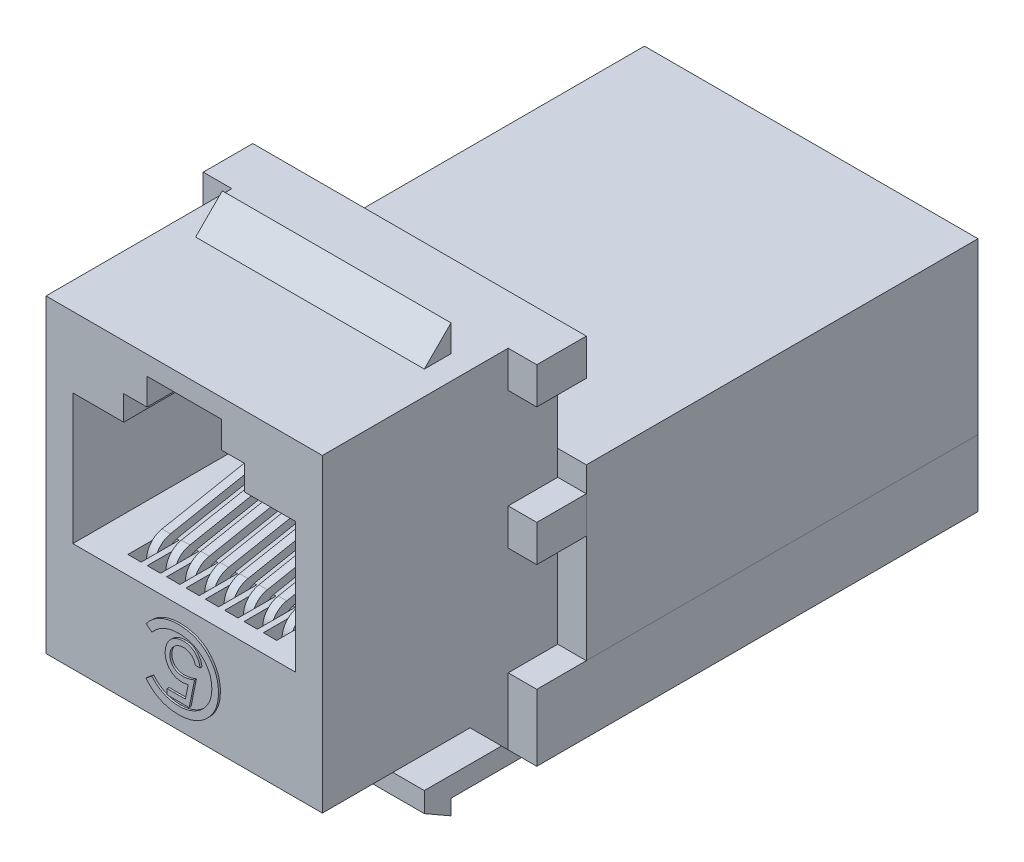
SolidWorks part; units mm, degrees
ref_plane "Front Plane" through (0, 0, 0) normal (0, 0, 1) x (1, 0, 0)
ref_plane "Top Plane" through (0, 0, 0) normal (0, 1, 0) x (1, 0, 0)
ref_plane "Right Plane" through (0, 0, 0) normal (1, 0, 0) x (0, 0, -1)
sketch "Sketch1" plane through (0, 0, 0) normal (0, 0, 1) x (1, 0, 0)
  line L1 (-7.25, 8.125) -> (7.25, 8.125)
  line L2 (-7.25, 8.125) -> (-7.25, -8.125)
  line L3 (-7.25, -8.125) -> (7.25, -8.125)
  line L4 (7.25, 8.125) -> (7.25, -8.125)
  line L5 (-7.25, 8.125) -> (7.25, -8.125) construction
  line L6 (-7.25, -8.125) -> (7.25, 8.125) construction
  point P0 (0, 0)
  dimension "D1" = 14.5
  dimension "D2" = 16.25
extrude "Boss-Extrude1" add sketch "Sketch1" against normal blind 12.35
sketch "Sketch2" plane through (0, 0, 0) normal (0, 0, 1) x (1, 0, 0)
  line L0 (-5.842, -2.425) -> (5.842, -2.425)
  line L1 (5.842, -2.425) -> (5.842, 4.425)
  line L2 (7.25, 8.125) -> (-7.25, 8.125) construction
  line L6 (5.842, 4.425) -> (3.175, 4.425)
  line L7 (3.175, 4.425) -> (3.175, 5.725)
  line L8 (3.175, 5.725) -> (1.95, 5.725)
  line L9 (1.95, 5.725) -> (1.95, 7.125)
  line L10 (1.95, 7.125) -> (-1.95, 7.125)
  line L11 (-1.95, 7.125) -> (-1.95, 5.725)
  line L12 (-1.95, 5.725) -> (-3.175, 5.725)
  line L13 (-3.175, 5.725) -> (-3.175, 4.425)
  line L14 (-3.175, 4.425) -> (-5.842, 4.425)
  line L19 (-5.842, 4.425) -> (-5.842, -2.425)
  line L20 (0, -1000) -> (0, 1000) construction
  line L22 (-3.175, 4.425) -> (-3.175, -2.425) construction
  dimension "D1" = 3.9
  dimension "D2" = 6.35
  dimension "D3" = 11.684
  dimension "D4" = 1
  dimension "D6" = 6.85
  dimension "D8" = 9.55
  dimension "D9" = 1.4
extrude "Cut-Extrude1" cut sketch "Sketch2" against normal blind 10
sketch "Sketch3" plane through (0, 0, -12.35) normal (0, 0, -1) x (-1, 0, 0)
  line L0 (-6.2, 7.125) -> (-6.2, 4.95)
  line L1 (-6.2, 4.95) -> (-3.175, 4.95)
  line L2 (-3.175, 4.95) -> (-3.175, 2.125)
  line L3 (-3.175, 2.125) -> (3.175, 2.125)
  line L4 (3.175, 2.125) -> (3.175, 4.95)
  line L5 (3.175, 4.95) -> (6.2, 4.95)
  line L6 (6.2, 4.95) -> (6.2, 7.125)
  line L7 (6.2, 7.125) -> (-6.2, 7.125)
  line L8 (-1.95, 7.125) -> (1.95, 7.125) construction
  line L9 (7.25, 8.125) -> (7.25, -8.125) construction
  line L10 (-7.25, -8.125) -> (-7.25, 8.125) construction
  line L12 (-3.175, 4.425) -> (-3.175, 5.725) construction
  line L13 (3.175, 5.725) -> (3.175, 4.425) construction
  dimension "D1" = 1.05
  dimension "D2" = 1.05
  dimension "D3" = 2.175
  dimension "D4" = 5
extrude "Cut-Extrude2" cut sketch "Sketch3" against normal blind 10.35
sketch "Sketch4" plane through (0, 0, -12.35) normal (0, 0, -1) x (-1, 0, 0)
  line L0 (7.25, -8.125) -> (-7.25, -8.125) construction
  line L1 (-8.75, -6.625) -> (8.75, -6.625)
  line L2 (-8.75, -6.625) -> (-8.75, -10.125)
  line L3 (-8.75, -10.125) -> (8.75, -10.125)
  line L4 (8.75, -6.625) -> (8.75, -10.125)
  line L5 (-8.75, -6.625) -> (8.75, -10.125) construction
  line L6 (-8.75, -10.125) -> (8.75, -6.625) construction
  point P0 (0, -8.375)
  dimension "D1" = 17.5
  dimension "D2" = 2
  dimension "D3" = 3.5
extrude "Boss-Extrude2" add sketch "Sketch4" along normal blind 20.55 and the other way blind 2.6
chamfer "Chamfer1" distance 2 angle 45 1 edges at (0, -8.125, -9.75)
sketch "Sketch5" plane through (0, 0, -12.35) normal (0, 0, -1) x (-1, 0, 0)
  line L0 (-7.25, -6.625) -> (-7.25, 8.125) construction
  line L1 (-8.75, 0.96) -> (-7.25, 0.96)
  line L2 (-8.75, 0.96) -> (-8.75, -0.96)
  line L3 (-8.75, -0.96) -> (-7.25, -0.96)
  line L4 (-7.25, 0.96) -> (-7.25, -0.96)
  line L5 (7.25, 8.125) -> (7.25, -6.625) construction
  line L6 (7.25, 0.96) -> (8.75, 0.96)
  line L7 (7.25, 0.96) -> (7.25, -0.96)
  line L8 (7.25, -0.96) -> (8.75, -0.96)
  line L9 (8.75, 0.96) -> (8.75, -0.96)
  line L10 (8.75, -10.125) -> (8.75, -6.625) construction
  line L11 (-7.25, 8.125) -> (-8.75, 8.125)
  line L12 (-7.25, 8.125) -> (-7.25, 6.205)
  line L13 (-7.25, 6.205) -> (-8.75, 6.205)
  line L14 (-8.75, 8.125) -> (-8.75, 6.205)
  line L15 (7.25, 8.125) -> (8.75, 8.125)
  line L16 (7.25, 8.125) -> (7.25, 6.205)
  line L17 (7.25, 6.205) -> (8.75, 6.205)
  line L18 (8.75, 8.125) -> (8.75, 6.205)
  point P24 (8.75, 0)
  dimension "D1" = 1.92
extrude "Boss-Extrude3" add sketch "Sketch5" against normal up to surface (2.6 mm away) up to face at (-8, -8.375, -9.75)
sketch "Sketch6" plane through (0, 0, 0) normal (1, 0, 0) x (0, 0, -1)
  line L0 (8, 9.525) -> (8, 8.125)
  line L1 (8, 8.125) -> (6.6, 8.125)
  line L2 (6.6, 8.125) -> (8, 9.525)
  line L3 (9.75, 8.125) -> (0, 8.125) construction
  line L4 (12.35, 6.205) -> (12.35, 8.125) construction
  line L5 (7.75, -8.125) -> (0, -8.125) construction
  dimension "D1" = 4.35
  dimension "D2" = 17.65
extrude "Boss-Extrude4" add sketch "Sketch6" along normal mid plane 12
sketch "Sketch7" plane through (0, 0, -12.35) normal (0, 0, -1) x (-1, 0, 0)
  line L0 (-7.25, -6.625) -> (7.25, -6.625) construction
  line L1 (-8.75, 2.275) -> (8.75, 2.275)
  line L2 (-8.75, 2.275) -> (-8.75, -6.625)
  line L3 (-8.75, -6.625) -> (8.75, -6.625)
  line L4 (8.75, 2.275) -> (8.75, -6.625)
  line L5 (-8.75, 2.275) -> (8.75, -6.625) construction
  line L6 (-8.75, -6.625) -> (8.75, 2.275) construction
  line L7 (-8.75, -10.125) -> (8.75, -10.125) construction
  line L9 (-8.75, 0.96) -> (-8.75, -0.96) construction
  line L11 (7.25, -5.8621) -> (-7.25, -5.8621)
  line L12 (7.25, -5.8621) -> (7.25, 1.5121)
  line L13 (7.25, 1.5121) -> (-7.25, 1.5121)
  line L14 (-7.25, -5.8621) -> (-7.25, 1.5121)
  line L15 (7.25, -5.8621) -> (-7.25, 1.5121) construction
  line L16 (7.25, 1.5121) -> (-7.25, -5.8621) construction
  point P0 (0, -2.175)
  point P10 (0, -2.175)
  dimension "D1" = 12.4
  dimension "D2" = 1.5
extrude "Boss-Extrude5" add sketch "Sketch7" along normal blind 20.55 separate body
sketch "Sketch8" plane through (0, 0, -32.9) normal (0, 0, -1) x (-1, 0, 0)
  line L1 (-7.25, 1.5121) -> (7.25, 1.5121)
  line L2 (-7.25, 1.5121) -> (-7.25, -5.8621)
  line L3 (-7.25, -5.8621) -> (7.25, -5.8621)
  line L4 (7.25, 1.5121) -> (7.25, -5.8621)
extrude "Boss-Extrude6" add sketch "Sketch8" against normal blind 1.5
sketch "Sketch9" plane through (0, 0, 0) normal (1, 0, 0) x (0, 0, -1)
  line L0 (17.9, -10.125) -> (17.9, -12.075)
  line L1 (17.9, -12.075) -> (8, -12.075)
  line L2 (8, -12.075) -> (8, -12.875)
  line L3 (8, -12.875) -> (6.6, -12.075)
  line L4 (6.6, -12.075) -> (6.6, -11.025)
  line L5 (6.6, -11.025) -> (14, -11.025)
  line L6 (14, -11.025) -> (14, -10.125)
  line L7 (14, -10.125) -> (17.9, -10.125)
  line L8 (9.75, -10.125) -> (32.9, -10.125) construction
  line L9 (8, 8.125) -> (8, 9.525) construction
  line L10 (9.75, 8.125) -> (0, 8.125) construction
  line L11 (32.9, -10.125) -> (32.9, -6.625) construction
  dimension "D1" = 20.2
  dimension "D2" = 1.05
  dimension "D3" = 22.4
  dimension "D4" = 3.9
  dimension "D5" = 15
extrude "Boss-Extrude7" add sketch "Sketch9" along normal mid plane 12
sketch "Sketch11" plane through (0, 0, 0) normal (0, 0, 1) x (1, 0, 0)
  line L0 (5.842, -3.325) -> (-5.842, -3.325) construction
  line L1 (-5.842, -2.425) -> (5.842, -2.425) construction
  line L2 (5.842, -3.925) -> (-5.842, -3.925) construction
  text T0 "C" font "Century Gothic" height 3.9
  text T1 "5" font "Century Gothic" height 2.8
  dimension "D1" = 0.9
  dimension "D2" = 0.6
extrude "Boss-Extrude8" add sketch "Sketch11" along normal blind 0.1
sketch "Sketch12" plane through (0, 0, -32.9) normal (0, 0, -1) x (-1, 0, 0)
  line L0 (0, -6.625) -> (0, 2.275) construction
  line L1 (8.75, -6.625) -> (-8.75, -6.625) construction
  line L2 (8.75, 2.275) -> (-8.75, 2.275) construction
  circle A0 centre (0, -2.175) radius 2
  point P9 (0, -2.175)
  dimension "D1" = 4
extrude "Cut-Extrude3" cut sketch "Sketch12" against normal up to next (1.5 mm away)
sketch "Sketch13" plane through (0, -2.425, 0) normal (0, 1, 0) x (1, 0, 0)
  line L0 (-5.842, 0) -> (5.842, 0) construction
  line L1 (-3.9052, 2.95) -> (-3.2067, 2.95)
  line L2 (-3.9052, 2.95) -> (-3.9052, 0.95)
  line L3 (-3.9052, 0.95) -> (-3.2067, 0.95)
  line L4 (-3.2067, 2.95) -> (-3.2067, 0.95)
  line L5 (-3.9052, 2.95) -> (-3.2067, 0.95) construction
  line L6 (-3.9052, 0.95) -> (-3.2067, 2.95) construction
  line L7 (-2.8892, 2.95) -> (-2.1907, 2.95)
  line L8 (-2.8892, 2.95) -> (-2.8892, 0.95)
  line L9 (-2.8892, 0.95) -> (-2.1907, 0.95)
  line L10 (-2.1907, 2.95) -> (-2.1907, 0.95)
  line L11 (-2.8892, 2.95) -> (-2.1907, 0.95) construction
  line L12 (-2.8892, 0.95) -> (-2.1907, 2.95) construction
  line L13 (-1.8732, 2.95) -> (-1.1747, 2.95)
  line L14 (-1.8732, 2.95) -> (-1.8732, 0.95)
  line L15 (-1.8732, 0.95) -> (-1.1747, 0.95)
  line L16 (-1.1747, 2.95) -> (-1.1747, 0.95)
  line L17 (-1.8732, 2.95) -> (-1.1747, 0.95) construction
  line L18 (-1.8732, 0.95) -> (-1.1747, 2.95) construction
  line L19 (-0.8572, 2.95) -> (-0.1587, 2.95)
  line L20 (-0.8572, 2.95) -> (-0.8572, 0.95)
  line L21 (-0.8572, 0.95) -> (-0.1587, 0.95)
  line L22 (-0.1587, 2.95) -> (-0.1587, 0.95)
  line L23 (-0.8572, 2.95) -> (-0.1587, 0.95) construction
  line L24 (-0.8572, 0.95) -> (-0.1587, 2.95) construction
  line L25 (0.1588, 2.95) -> (0.8573, 2.95)
  line L26 (0.1588, 2.95) -> (0.1588, 0.95)
  line L27 (0.1588, 0.95) -> (0.8573, 0.95)
  line L28 (0.8573, 2.95) -> (0.8573, 0.95)
  line L29 (0.1588, 2.95) -> (0.8573, 0.95) construction
  line L30 (0.1588, 0.95) -> (0.8573, 2.95) construction
  line L31 (1.1747, 2.95) -> (1.8733, 2.95)
  line L32 (1.1747, 2.95) -> (1.1748, 0.95)
  line L33 (1.1748, 0.95) -> (1.8733, 0.95)
  line L34 (1.8733, 2.95) -> (1.8733, 0.95)
  line L35 (1.1747, 2.95) -> (1.8733, 0.95) construction
  line L36 (1.1748, 0.95) -> (1.8733, 2.95) construction
  line L37 (2.1908, 2.95) -> (2.8893, 2.95)
  line L38 (2.1908, 2.95) -> (2.1908, 0.95)
  line L39 (2.1908, 0.95) -> (2.8893, 0.95)
  line L40 (2.8893, 2.95) -> (2.8893, 0.95)
  line L41 (2.1908, 2.95) -> (2.8893, 0.95) construction
  line L42 (2.1908, 0.95) -> (2.8893, 2.95) construction
  line L43 (3.2068, 2.95) -> (3.9053, 2.95)
  line L44 (3.2068, 2.95) -> (3.2068, 0.95)
  line L45 (3.2068, 0.95) -> (3.9053, 0.95)
  line L46 (3.9053, 2.95) -> (3.9053, 0.95)
  line L47 (3.2068, 2.95) -> (3.9053, 0.95) construction
  line L48 (3.2068, 0.95) -> (3.9053, 2.95) construction
  line L49 (0, -1000) -> (0, 49000) construction
  point P0 (-3.556, 1.95)
  point P7 (-2.54, 1.95)
  point P12 (-1.524, 1.95)
  point P17 (-0.508, 1.95)
  point P22 (0.508, 1.95)
  point P27 (1.524, 1.95)
  point P32 (2.54, 1.95)
  point P37 (3.556, 1.95)
  point P45 (0, 0)
  dimension "D1" = 0.95
  dimension "D2" = 0.6985
  dimension "D3" = 2.95
  dimension "D4" = 0.6985
  dimension "D5" = 1.016
  dimension "D6" = 0.6985
  dimension "D7" = 0.6985
  dimension "D8" = 1.016
  dimension "D9" = 1.016
  dimension "D10" = 0.6985
  dimension "D11" = 0.6985
  dimension "D12" = 1.016
  dimension "D13" = 0.6985
  dimension "D14" = 0.6985
  dimension "D15" = 1.016
  dimension "D16" = 1.016
  dimension "D17" = 1.016
extrude "Cut-Extrude4" cut sketch "Sketch13" against normal blind 1
sketch "Sketch14" plane through (0, 0, -10) normal (0, 0, 1) x (1, 0, 0)
  line L0 (-3.9052, -0.425) -> (-3.2067, -0.425)
  line L1 (-3.9052, -0.425) -> (-3.9052, -2.425)
  line L2 (-3.9052, -2.425) -> (-3.2067, -2.425)
  line L3 (-3.2067, -0.425) -> (-3.2067, -2.425)
  line L4 (-3.9052, -0.425) -> (-3.2067, -2.425) construction
  line L5 (-3.9052, -2.425) -> (-3.2067, -0.425) construction
  line L6 (-2.8893, -0.425) -> (-2.1907, -0.425)
  line L7 (-2.8893, -0.425) -> (-2.8892, -2.425)
  line L8 (-2.8892, -2.425) -> (-2.1907, -2.425)
  line L9 (-2.1907, -0.425) -> (-2.1907, -2.425)
  line L10 (-2.8893, -0.425) -> (-2.1907, -2.425) construction
  line L11 (-2.8892, -2.425) -> (-2.1907, -0.425) construction
  line L12 (-1.8733, -0.425) -> (-1.1747, -0.425)
  line L13 (-1.8733, -0.425) -> (-1.8732, -2.425)
  line L14 (-1.8732, -2.425) -> (-1.1747, -2.425)
  line L15 (-1.1747, -0.425) -> (-1.1747, -2.425)
  line L16 (-1.8733, -0.425) -> (-1.1747, -2.425) construction
  line L17 (-1.8732, -2.425) -> (-1.1747, -0.425) construction
  line L18 (-0.8573, -0.425) -> (-0.1588, -0.425)
  line L19 (-0.8573, -0.425) -> (-0.8572, -2.425)
  line L20 (-0.8572, -2.425) -> (-0.1587, -2.425)
  line L21 (-0.1588, -0.425) -> (-0.1587, -2.425)
  line L22 (-0.8573, -0.425) -> (-0.1587, -2.425) construction
  line L23 (-0.8572, -2.425) -> (-0.1588, -0.425) construction
  line L24 (0.1587, -0.425) -> (0.8572, -0.425)
  line L25 (0.1587, -0.425) -> (0.1588, -2.425)
  line L26 (0.1588, -2.425) -> (0.8573, -2.425)
  line L27 (0.8572, -0.425) -> (0.8573, -2.425)
  line L28 (0.1587, -0.425) -> (0.8573, -2.425) construction
  line L29 (0.1588, -2.425) -> (0.8572, -0.425) construction
  line L30 (1.1747, -0.425) -> (1.8732, -0.425)
  line L31 (1.1747, -0.425) -> (1.1747, -2.425)
  line L32 (1.1747, -2.425) -> (1.8733, -2.425)
  line L33 (1.8732, -0.425) -> (1.8733, -2.425)
  line L34 (1.1747, -0.425) -> (1.8733, -2.425) construction
  line L35 (1.1747, -2.425) -> (1.8732, -0.425) construction
  line L36 (2.1907, -0.425) -> (2.8893, -0.425)
  line L37 (2.1907, -0.425) -> (2.1908, -2.425)
  line L38 (2.1908, -2.425) -> (2.8893, -2.425)
  line L39 (2.8893, -0.425) -> (2.8893, -2.425)
  line L40 (2.1907, -0.425) -> (2.8893, -2.425) construction
  line L41 (2.1908, -2.425) -> (2.8893, -0.425) construction
  line L42 (3.2067, -0.425) -> (3.9052, -0.425)
  line L43 (3.2067, -0.425) -> (3.2067, -2.425)
  line L44 (3.2067, -2.425) -> (3.9052, -2.425)
  line L45 (3.9052, -0.425) -> (3.9052, -2.425)
  line L46 (3.2067, -0.425) -> (3.9052, -2.425) construction
  line L47 (3.2067, -2.425) -> (3.9052, -0.425) construction
  line L48 (0, -1003.6041) -> (0, 48996.3959) construction
  line L49 (-5.842, -2.425) -> (5.842, -2.425) construction
  line L50 (-4.9213, -0.425) -> (-4.2227, -0.425)
  line L51 (-4.9213, -0.425) -> (-4.9213, -2.425)
  line L52 (-4.9213, -2.425) -> (-4.2227, -2.425)
  line L53 (-4.2227, -0.425) -> (-4.2227, -2.425)
  line L54 (-4.9213, -0.425) -> (-4.2227, -2.425) construction
  line L55 (-4.9213, -2.425) -> (-4.2227, -0.425) construction
  line L56 (4.2227, -0.425) -> (4.9212, -0.425)
  line L57 (4.2227, -0.425) -> (4.2227, -2.425)
  line L58 (4.2227, -2.425) -> (4.9212, -2.425)
  line L59 (4.9212, -0.425) -> (4.9212, -2.425)
  line L60 (4.2227, -0.425) -> (4.9212, -2.425) construction
  line L61 (4.2227, -2.425) -> (4.9212, -0.425) construction
  point P0 (-3.556, -1.425)
  point P5 (-2.54, -1.425)
  point P10 (-1.524, -1.425)
  point P15 (-0.508, -1.425)
  point P20 (0.508, -1.425)
  point P25 (1.524, -1.425)
  point P30 (2.54, -1.425)
  point P35 (3.556, -1.425)
  point P45 (-4.572, -1.425)
  point P50 (4.572, -1.425)
  dimension "D1" = 0.6985
  dimension "D2" = 0.6985
  dimension "D3" = 1.016
  dimension "D4" = 0.6985
  dimension "D5" = 0.6985
  dimension "D6" = 1.016
  dimension "D7" = 1.016
  dimension "D8" = 0.6985
  dimension "D9" = 0.6985
  dimension "D10" = 1.016
  dimension "D11" = 0.6985
  dimension "D12" = 0.6985
  dimension "D13" = 1.016
  dimension "D14" = 1.016
  dimension "D15" = 1.016
  dimension "D16" = 2
  dimension "D17" = 0.6985
  dimension "D18" = 2
  dimension "D19" = 1.016
  dimension "D20" = 0.6985
  dimension "D21" = 2
  dimension "D22" = 1.016
extrude "Cut-Extrude5" cut sketch "Sketch14" against normal blind 1
ref_plane "Plane2" through (-3.7782, 0, 0) normal (1, 0, 0) x (0, 0, -1)
sketch "Sketch15" plane through (-3.7782, 0, 0) normal (1, 0, 0) x (0, 0, -1)
  line L0 (11, -0.425) -> (2.617, -2.0337)
  line L1 (1.8055, -3.0158) -> (1.8055, -3.425)
  line L2 (1.8055, -3.425) -> (2.25, -3.425)
  line L3 (2.25, -3.425) -> (2.25, -3.375)
  line L4 (3.0615, -2.3929) -> (11, -0.8695)
  line L5 (11, -0.8695) -> (11, -0.425)
  line L6 (11, -0.425) -> (11, -2.425) construction
  line L9 (2.95, -3.425) -> (0.95, -3.425) construction
  arc A0 (2.25, -3.375) -> (3.0615, -2.3929) centre (3.25, -3.375) cw
  arc A1 (2.617, -2.0337) -> (1.8055, -3.0158) centre (2.8055, -3.0158) ccw
  dimension "D3" = 1
  dimension "D1" = 0.4445
  dimension "D2" = 0.4445
  dimension "D4" = 0.7
  dimension "D5" = 0.05
extrude "Boss-Extrude9" add sketch "Sketch15" along normal blind 0.4445 separate body
pattern_linear "LPattern4" count 8 spacing 1.016 along (1, 0, 0) of bodies 116
other "CPoint1" parameters "Diameter"=5.5, "StubLength"=2
ref_axis "Axis1" through (0, -2.175, -41.4) along (0, 0, 1)
